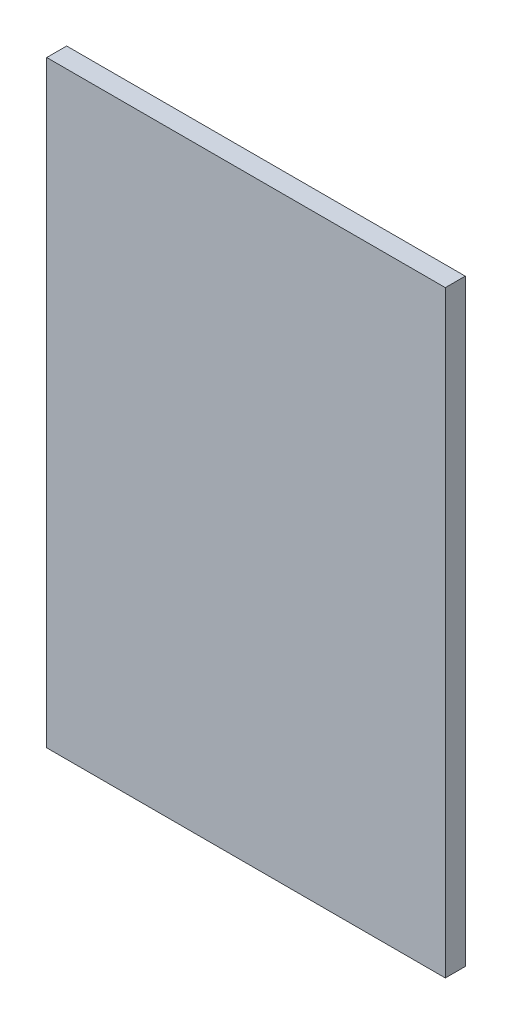
SolidWorks part; units mm, degrees
material "轻木"
ref_plane "前视基准面" through (0, 0, 0) normal (0, 0, 1) x (1, 0, 0)
ref_plane "上视基准面" through (0, 0, 0) normal (0, 1, 0) x (1, 0, 0)
ref_plane "右视基准面" through (0, 0, 0) normal (1, 0, 0) x (0, 0, -1)
sketch "Sketch1" plane through (0, 0, 0) normal (0, 0, 1) x (1, 0, 0)
  line L1 (-100, 150) -> (100, 150)
  line L2 (-100, 150) -> (-100, -150)
  line L3 (-100, -150) -> (100, -150)
  line L4 (100, 150) -> (100, -150)
  point P4 (-300, 150)
  dimension "D1" = 100
  dimension "D2" = 100
  dimension "D3" = 150
  dimension "D4" = 150
extrude "Extrude1" add sketch "Sketch1" along normal blind 10
